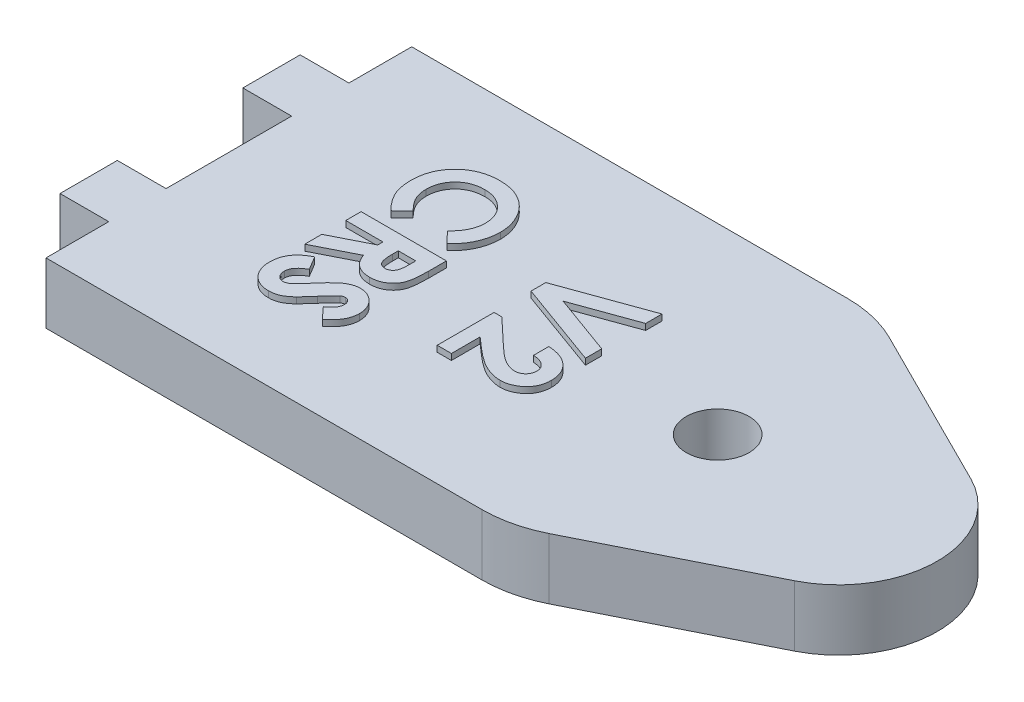
SolidWorks part; units mm, degrees
ref_plane "Front Plane" through (0, 0, 0) normal (0, 0, 1) x (1, 0, 0)
ref_plane "Top Plane" through (0, 0, 0) normal (0, 1, 0) x (1, 0, 0)
ref_plane "Right Plane" through (0, 0, 0) normal (1, 0, 0) x (0, 0, -1)
sketch "Sketch1" plane through (0, 0, 0) normal (0, 1, 0) x (1, 0, 0)
  line L0 (0, 0) -> (0, 10)
  line L13 (0, 10) -> (-8, 10)
  line L14 (-8, 10) -> (-8, 20)
  line L16 (-8, 20) -> (0, 20)
  line L17 (0, 20) -> (0, 40)
  line L18 (0, 40) -> (-8, 40)
  line L19 (-8, 40) -> (-8, 50)
  line L20 (-8, 50) -> (0, 50)
  line L21 (0, 50) -> (0, 60)
  line L22 (0, 60) -> (50, 60)
  line L23 (50, 60) -> (90, 40)
  line L24 (90, 40) -> (90, 20)
  line L25 (90, 20) -> (50, 0)
  line L26 (50, 0) -> (0, 0)
  dimension "D1" = 10
  dimension "D2" = 10
  dimension "D3" = 20
  dimension "D4" = 10
  dimension "D5" = 10
  dimension "D6" = 8
  dimension "D7" = 8
  dimension "D8" = 50
  dimension "D9" = 40
  dimension "D10" = 50
  dimension "D11" = 20
  dimension "D12" = 20
extrude "Boss-Extrude2" add sketch "Sketch1" along normal blind 10
sketch "Sketch5" plane through (0, 10, 0) normal (0, 1, 0) x (1, 0, 0)
  line L0 (90, 40) -> (50, 60) construction
  line L1 (50, 0) -> (90, 20) construction
  line L2 (90, 20) -> (90, 40) construction
  line L3 (81.0557, 44.4721) -> (90, 40)
  line L4 (90, 40) -> (90, 20)
  line L5 (90, 20) -> (81.0557, 15.5279)
  arc A0 (81.0557, 44.4721) -> (81.0557, 15.5279) centre (73.8197, 30) cw
  line M2 (50, 0) -> (90, 20)
  line M3 (90, 20) -> (90, 40)
  line M4 (90, 40) -> (50, 60)
extrude "Cut-Extrude2" cut sketch "Sketch5" against normal blind 10 contours A0 L4 M4 | A0 M3 M2 region at (88.1125, 10, -21.1665) region at (88.1125, 10, -38.8335)
fillet "Fillet3" radius 16 2 edges at (50, 5, -60) (50, 5, 0)
sketch "Sketch8" plane through (0, 10, 0) normal (0, 1, 0) x (1, 0, 0)
  line L0 (-8, 50) -> (-8, 40) construction
  line L1 (0, 50) -> (-8, 50)
  line L2 (0, 50) -> (0, 49.7)
  line L3 (0, 49.7) -> (-8, 49.7)
  line L4 (-8, 50) -> (-8, 49.7)
  line L6 (0, 40) -> (-8, 40)
  line L7 (0, 40) -> (0, 40.3)
  line L8 (0, 40.3) -> (-8, 40.3)
  line L9 (-8, 40) -> (-8, 40.3)
  line L11 (-8, 20) -> (-8, 19.7)
  line L12 (0, 19.7) -> (-8, 19.7)
  line L13 (0, 20) -> (0, 19.7)
  line L14 (0, 20) -> (-8, 20)
  line L15 (-8, 10) -> (-8, 10.3)
  line L16 (0, 10.3) -> (-8, 10.3)
  line L17 (0, 10) -> (0, 10.3)
  line L18 (0, 10) -> (-8, 10)
  dimension "D1" = 0.3
  dimension "D2" = 0.3
extrude "Cut-Extrude5" cut sketch "Sketch8" against normal blind 10
sketch "Sketch11" plane through (0, 0, 0) normal (0, -1, 0) x (1, 0, 0)
  line L0 (46.2229, 0) -> (76.2229, 0)
  line L1 (76.2229, 0) -> (107.2786, -15.5279)
  line L2 (46.2229, 0) -> (46.2229, -60)
  line L3 (46.2229, -60) -> (76.2229, -60)
  line L4 (76.2229, -60) -> (107.2786, -44.4721)
  line L5 (53.3783, -1.6892) -> (81.0557, -15.5279) construction
  line L6 (81.0557, -44.4721) -> (53.3783, -58.3108) construction
  arc A0 (107.2786, -44.4721) -> (107.2786, -15.5279) centre (100.0426, -30) ccw
  arc A1 (81.0557, -44.4721) -> (81.0557, -15.5279) centre (73.8197, -30) ccw construction
  dimension "D1" = 30
extrude "Boss-Extrude3" add sketch "Sketch11" against normal blind 10
sketch "Sketch12" plane through (0, 10, 0) normal (0, 1, 0) x (1, 0, 0)
  circle A0 centre (80.2029, 30) radius 5.15
  arc A1 (107.2786, 15.5279) -> (107.2786, 44.4721) centre (100.0426, 30) ccw construction
  point P2 (116.2229, 30)
  dimension "D1" = 36.02
  dimension "D2" = 10.3
fillet "Fillet4" radius 20 2 edges at (76.2229, 5, 0) (76.2229, 5, -60)
sketch "Sketch13" plane through (0, 10, 0) normal (0, 1, 0) x (1, 0, 0)
  line L0 (45.5054, 51.8965) -> (45.5054, 7.8991) construction
  text T0 "<b>V2</b>\r\n<b>CRS</b>" font "Century Gothic" height 14
extrude "Cut-Extrude6" cut sketch "Sketch12" against normal blind 10
extrude "Boss-Extrude4" add sketch "Sketch13" along normal blind 1
